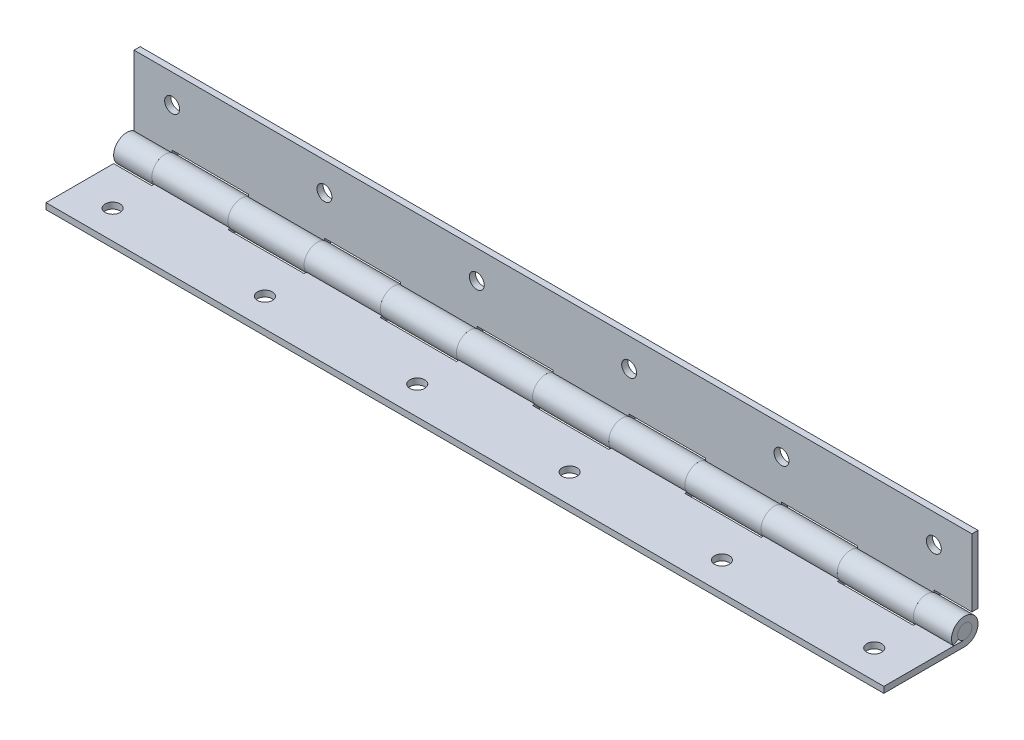
SolidWorks part; units mm, degrees
material "2024-T3"
ref_plane "Front Plane" through (0, 0, 0) normal (0, 0, 1) x (1, 0, 0)
ref_plane "Top Plane" through (0, 0, 0) normal (0, 1, 0) x (1, 0, 0)
ref_plane "Right Plane" through (0, 0, 0) normal (1, 0, 0) x (0, 0, -1)
sketch "Sketch1" plane through (0, 0, 0) normal (1, 0, 0) x (0, 0, -1)
  line L0 (0, -2.2098) -> (-13.4874, -2.2098)
  line L1 (-13.4874, -2.2098) -> (-13.4874, -1.1938)
  line L2 (-13.4874, -1.1938) -> (0, -1.1938)
  line L3 (-1.0455, -0.5763) -> (-1.9352, -1.0668)
  arc A0 (0, -1.1938) -> (-1.0455, -0.5763) centre (0, 0) ccw
  arc A1 (0, -2.2098) -> (-1.9352, -1.0668) centre (0, 0) ccw
  dimension "D2" = 2.3876
  dimension "D1" = 1.016
  dimension "D3" = 13.4874
  dimension "D4" = 0.127
extrude "Boss-Extrude1" add sketch "Sketch1" along normal blind 139.7 contours A1 L3 A0 L2 L1 L0
sketch "Sketch2" plane through (0, -1.1938, 0) normal (0, 1, 0) x (1, 0, 0)
  line L0 (0, -13.4874) -> (0, 0) construction
  circle A0 centre (6.35, -8.7376) radius 1.2446
  dimension "D2" = 2.4892
  dimension "D1" = 6.35
  dimension "D3" = 8.7376
extrude "Cut-Extrude1" cut sketch "Sketch2" against normal through all
pattern_linear "LPattern1" count 6 spacing 25.4 along (1, 0, 0) of "Cut-Extrude1"
ref_axis "Axis1" through (-6.985, 0, 0) along (1, 0, 0)
ref_plane "HINGE ANGLE" through (0, 0, 0) normal (0, 0, 1) x (1, 0, 0)
ref_plane "Plane1" through (0, 0, 0) normal (0, 0.7071, -0.7071) x (-1, 0, 0)
mirror "Mirror1" about plane through (0, 0, 0) normal (0, 0.7071, -0.7071) of bodies 103
sketch "Sketch3" plane through (0, -2.2098, 0) normal (0, -1, 0) x (1, 0, 0)
  line L0 (6.35, 8.7376) -> (6.35, 2.2098) construction
  line L1 (0, -2.2098) -> (6.35, -2.2098)
  line L2 (0, -2.2098) -> (0, 2.2098)
  line L3 (0, 2.2098) -> (6.35, 2.2098)
  line L4 (6.35, -2.2098) -> (6.35, 2.2098)
  line L5 (139.7, 2.2098) -> (0, 2.2098) construction
  line L6 (31.75, 8.7376) -> (31.75, 2.2098) construction
  line L7 (31.75, 2.2098) -> (19.05, 2.2098)
  line L8 (31.75, 2.2098) -> (31.75, -2.2098)
  line L9 (31.75, -2.2098) -> (19.05, -2.2098)
  line L10 (19.05, 2.2098) -> (19.05, -2.2098)
  line L11 (57.15, 2.2098) -> (44.45, 2.2098)
  line L12 (57.15, 2.2098) -> (57.15, -2.2098)
  line L13 (57.15, -2.2098) -> (44.45, -2.2098)
  line L14 (44.45, 2.2098) -> (44.45, -2.2098)
  line L15 (82.55, 2.2098) -> (69.85, 2.2098)
  line L16 (82.55, 2.2098) -> (82.55, -2.2098)
  line L17 (82.55, -2.2098) -> (69.85, -2.2098)
  line L18 (69.85, 2.2098) -> (69.85, -2.2098)
  line L19 (107.95, 2.2098) -> (95.25, 2.2098)
  line L20 (107.95, 2.2098) -> (107.95, -2.2098)
  line L21 (107.95, -2.2098) -> (95.25, -2.2098)
  line L22 (95.25, 2.2098) -> (95.25, -2.2098)
  line L23 (57.15, 8.7376) -> (57.15, 2.2098) construction
  line L24 (82.55, 8.7376) -> (82.55, 2.2098) construction
  line L25 (107.95, 8.7376) -> (107.95, 2.2098) construction
  line L26 (133.35, 8.7376) -> (133.35, 2.2098) construction
  line L27 (120.65, -2.2098) -> (133.35, -2.2098)
  line L28 (120.65, -2.2098) -> (120.65, 2.2098)
  line L29 (120.65, 2.2098) -> (133.35, 2.2098)
  line L30 (133.35, -2.2098) -> (133.35, 2.2098)
  dimension "D1" = 12.7
extrude "Cut-Extrude2" cut sketch "Sketch3" against normal through all
sketch "Sketch4" plane through (0, 0, -2.2098) normal (0, 0, -1) x (-1, 0, 0)
  line L0 (-6.35, 2.2098) -> (-19.05, 2.2098) construction
  line L1 (-6.35, 2.2098) -> (-19.05, 2.2098)
  line L2 (-6.35, 2.2098) -> (-6.35, -2.2098)
  line L3 (-6.35, -2.2098) -> (-19.05, -2.2098)
  line L4 (-19.05, 2.2098) -> (-19.05, -2.2098)
  line L5 (-139.7, -2.2098) -> (0, -2.2098) construction
  line L6 (-133.35, 8.7376) -> (-133.35, 2.2098) construction
  line L7 (-6.35, 8.7376) -> (-6.35, 2.2098) construction
  line L8 (-107.95, 8.7376) -> (-107.95, 2.2098) construction
  line L9 (-31.75, 2.2098) -> (-44.45, 2.2098)
  line L10 (-31.75, 2.2098) -> (-31.75, -2.2098)
  line L11 (-31.75, -2.2098) -> (-44.45, -2.2098)
  line L12 (-44.45, 2.2098) -> (-44.45, -2.2098)
  line L13 (-57.15, 2.2098) -> (-69.85, 2.2098)
  line L14 (-57.15, 2.2098) -> (-57.15, -2.2098)
  line L15 (-57.15, -2.2098) -> (-69.85, -2.2098)
  line L16 (-69.85, 2.2098) -> (-69.85, -2.2098)
  line L17 (-82.55, 2.2098) -> (-95.25, 2.2098)
  line L18 (-82.55, 2.2098) -> (-82.55, -2.2098)
  line L19 (-82.55, -2.2098) -> (-95.25, -2.2098)
  line L20 (-95.25, 2.2098) -> (-95.25, -2.2098)
  line L21 (-107.95, 2.2098) -> (-120.65, 2.2098)
  line L22 (-107.95, 2.2098) -> (-107.95, -2.2098)
  line L23 (-107.95, -2.2098) -> (-120.65, -2.2098)
  line L24 (-120.65, 2.2098) -> (-120.65, -2.2098)
  line L25 (-82.55, 8.7376) -> (-82.55, 2.2098) construction
  line L26 (-57.15, 8.7376) -> (-57.15, 2.2098) construction
  line L28 (-31.75, 8.7376) -> (-31.75, 2.2098) construction
  line L29 (-133.35, 2.2098) -> (-139.7, 2.2098)
  line L30 (-133.35, 2.2098) -> (-133.35, -2.2098)
  line L31 (-133.35, -2.2098) -> (-139.7, -2.2098)
  line L32 (-139.7, 2.2098) -> (-139.7, -2.2098)
  dimension "D1" = 12.7
extrude "Cut-Extrude3" cut sketch "Sketch4" against normal through all
sketch "Sketch5" plane through (0, 0, 0) normal (-1, 0, 0) x (0, 0, 1)
  circle A0 centre (0, 0) radius 1.1938
  arc A1 (-1.1938, 0) -> (-0.5763, 1.0455) centre (0, 0) ccw construction
extrude "Boss-Extrude2" add sketch "Sketch5" against normal up to surface (139.7 mm away) separate body up to face at (139.7, -0.4994, 4.4557)
